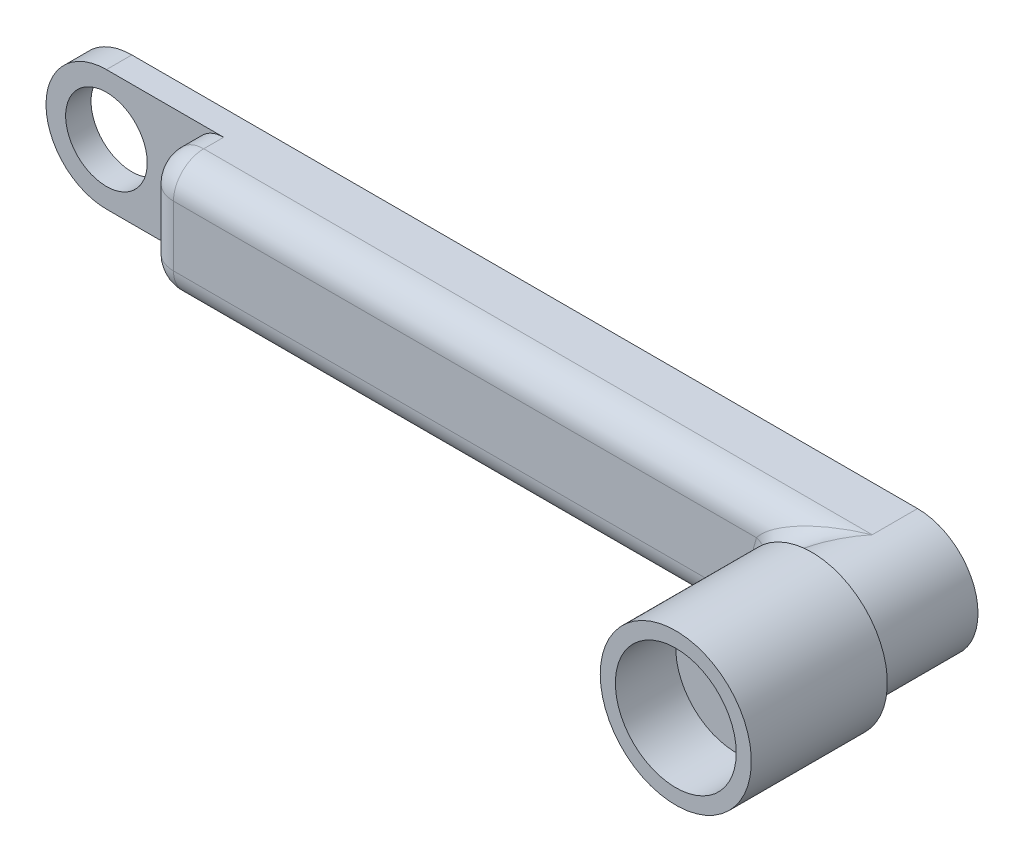
SolidWorks part; units mm, degrees
ref_plane "Front Plane" through (0, 0, 0) normal (0, 0, 1) x (1, 0, 0)
ref_plane "Top Plane" through (0, 0, 0) normal (0, 1, 0) x (1, 0, 0)
ref_plane "Right Plane" through (0, 0, 0) normal (1, 0, 0) x (0, 0, -1)
sketch "Sketch1" plane through (0, 0, 0) normal (0, 0, 1) x (1, 0, 0)
  line L0 (-159.9449, 0) -> (100.0551, 0) construction
  line L1 (-159.9449, 20) -> (100.0551, 20)
  line L2 (-159.9449, -20) -> (100.0551, -20)
  arc A0 (-159.9449, 20) -> (-159.9449, -20) centre (-159.9449, 0) ccw
  arc A1 (100.0551, -20) -> (100.0551, 20) centre (100.0551, 0) ccw
  point P3 (-29.9449, 0)
  point P8 (-179.9449, 0)
  point P9 (120.0551, 0)
  dimension "D2" = 20
  dimension "D1" = 300
extrude "Boss-Extrude1" add sketch "Sketch1" along normal blind 25
sketch "Sketch2" plane through (0, 0, 25) normal (0, 0, 1) x (1, 0, 0)
  circle A0 centre (100.0551, 0) radius 20
  dimension "D1" = 40
sketch "Sketch3" plane through (0, 0, 25) normal (0, 0, 1) x (1, 0, 0)
  circle A0 centre (-159.9449, 0) radius 13.5
  dimension "D1" = 27
extrude "Cut-Extrude2" cut sketch "Sketch3" against normal blind 25
sketch "Sketch7" plane through (0, 0, 25) normal (0, 0, 1) x (1, 0, 0)
  circle A0 centre (-159.9449, 0) radius 13.4686
extrude "Boss-Extrude4" add sketch "Sketch7" against normal blind 3 separate body
sketch "Sketch9" plane through (0, 0, 25) normal (0, 0, 1) x (1, 0, 0)
  line L0 (-131.155, 20) -> (-131.155, -20)
  line L1 (100.0551, 20) -> (-159.9449, 20) construction
  line L2 (-159.9449, -20) -> (100.0551, -20) construction
  line L3 (-131.155, -20) -> (-159.9449, -20)
  line L5 (-159.9449, 20) -> (-131.155, 20)
  arc A0 (-159.9449, 20) -> (-159.9449, -20) centre (-159.9449, 0) ccw
extrude "Cut-Extrude4" cut sketch "Sketch9" against normal blind 16.6
extrude "Boss-Extrude5" add sketch "Sketch2" along normal blind 10
sketch "Sketch10" plane through (0, 0, 35) normal (0, 0, 1) x (1, 0, 0)
  circle A0 centre (100.0551, 0) radius 25
  dimension "D1" = 50
extrude "Boss-Extrude6" add sketch "Sketch10" along normal blind 45
sketch "Sketch11" plane through (0, 0, 80) normal (0, 0, 1) x (1, 0, 0)
  circle A0 centre (100.0551, 0) radius 20
  dimension "D1" = 40
extrude "Cut-Extrude5" cut sketch "Sketch11" against normal blind 20
fillet "Fillet1" radius 10 1 edges at (-131.155, 0, 25)
fillet "Fillet2" radius 10 7 edges at (-131.155, -20, 11.7) (-128.226, -20, 22.0711) (-131.155, 20, 11.7) (-128.226, 20, 22.0711) (80.0551, 0, 25) (-10.5499, -20, 25) (-10.5499, 20, 25)
